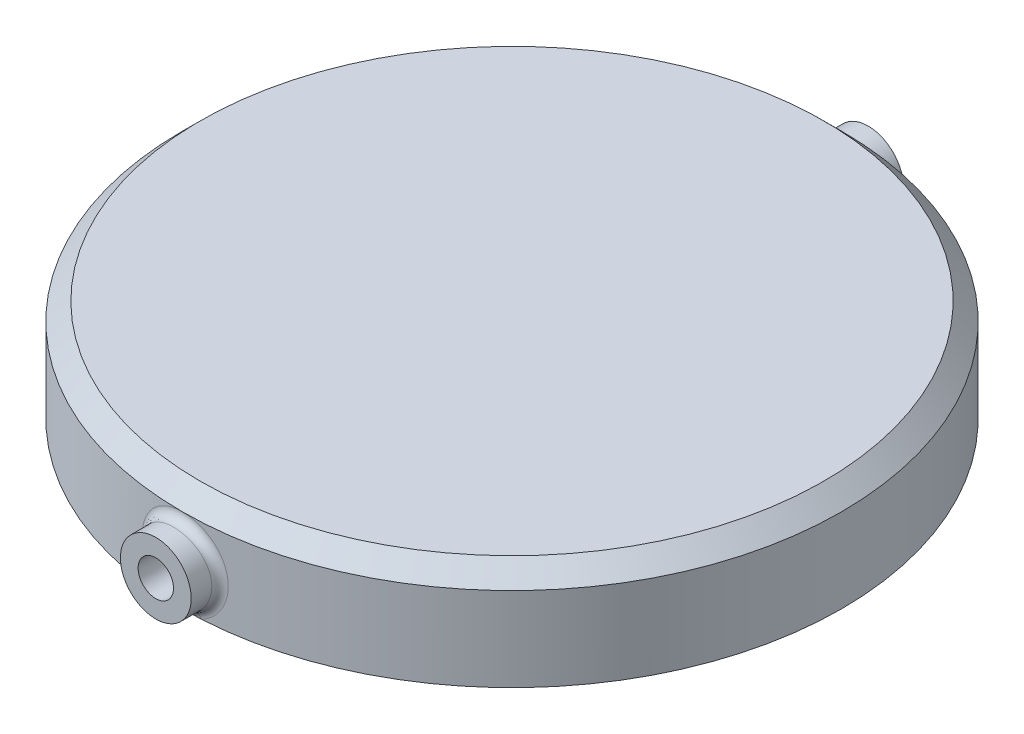
SolidWorks part; units mm, degrees
ref_plane "Front Plane" through (0, 0, 0) normal (0, 0, 1) x (1, 0, 0)
ref_plane "Top Plane" through (0, 0, 0) normal (0, 1, 0) x (1, 0, 0)
ref_plane "Right Plane" through (0, 0, 0) normal (1, 0, 0) x (0, 0, -1)
sketch "Sketch1" plane through (0, 0, 0) normal (0, 1, 0) x (1, 0, 0)
  line L0 (0, 0) -> (0, 13.7725) construction
  line L1 (0, 0) -> (-10.9504, 0) construction
  circle A0 centre (0, 0) radius 35.5
  circle A1 centre (0, 0) radius 35 construction
  circle A2 centre (0, 0) radius 37.25
  circle A3 centre (0, 0) radius 30
  dimension "D1" = 71
  dimension "D2" = 70
  dimension "D3" = 1.75
  dimension "D4" = 60
extrude "Boss-Extrude1" add sketch "Sketch1" against normal blind 10 contours A2 A0 region at (-36.1964, 0, 0)
extrude "Boss-Extrude2" add sketch "Sketch1<2>" along normal blind 1.5 contours A0 | A2 A0 | A3 region at (-34.4959, 0, 0) region at (-36.1964, 0, 0) region at (0, 0, 0)
sketch "Sketch1<2>" plane through (0, 0, 0) normal (0, 1, 0) x (1, 0, 0) same geometry as "Sketch1"
chamfer "Chamfer1" distance 1.5 angle 45 1 edges at (0, 0, 35.5)
chamfer "Chamfer2" distance 2 angle 45 1 edges at (0, 1.5, 37.25)
ref_plane "Plane1" through (0, 0, 37.25) normal (0, 0, 1) x (1, 0, 0)
sketch "Sketch2" plane through (0, 0, 37.25) normal (0, 0, 1) x (1, 0, 0)
  line L0 (0, -0.5) -> (0, -10) construction
  line L1 (-37.25, -0.5) -> (37.25, -0.5) construction
  line L2 (-37.25, -10) -> (37.25, -10) construction
  circle A0 centre (0, -5.5) radius 2
  circle A1 centre (0, -5.5) radius 4
  dimension "D1" = 4
  dimension "D2" = 2
  dimension "D3" = 5
extrude "Cut-Extrude1" cut sketch "Sketch2" against normal blind 10 contours L0 A0 | A0 L0 region at (0.8488, -5.5, 37.25) region at (-0.8488, -5.5, 37.25)
extrude "Boss-Extrude4" add sketch "Sketch2<3>" along normal blind 3 and the other way blind 1 contours A1 L0 A0 | L0 A1 A0 region at (2.7652, -2.7348, 37.25) region at (-0.0894, -2.5, 37.25)
sketch "Sketch2<3>" plane through (0, 0, 37.25) normal (0, 0, 1) x (1, 0, 0) same geometry as "Sketch2"
mirror "Mirror1" about plane through (0, 0, 0) normal (0, 0, 1) of "Boss-Extrude4", "Cut-Extrude1"
ref_plane "Plane2" through (37.25, 0, 0) normal (1, 0, 0) x (0, 0, -1)
sketch "tirangle" plane through (37.25, 0, 0) normal (1, 0, 0) x (0, 0, -1)
  line L0 (0, -0.5) -> (0, -13.8889) construction
  line L2 (2.5, -0.5) -> (-2.5, -0.5)
  line L6 (-2.5, -0.5) -> (0, -3)
  line L7 (-37.25, -0.5) -> (37.25, -0.5) construction
  line L8 (0, -3) -> (2.5, -0.5)
  dimension "D1" = 45
  dimension "D2" = 5
extrude "Boss-Extrude6" add sketch "tirangle" against normal blind 5 from offset 1 offset against normal yes
mirror "Mirror2" about plane through (0, 0, 0) normal (1, 0, 0) of "Boss-Extrude6"
fillet "Fillet1" radius 1 2 edges at (3.8988, -4.6059, -37.0454) (-0.8941, -1.6012, 37.2393)
